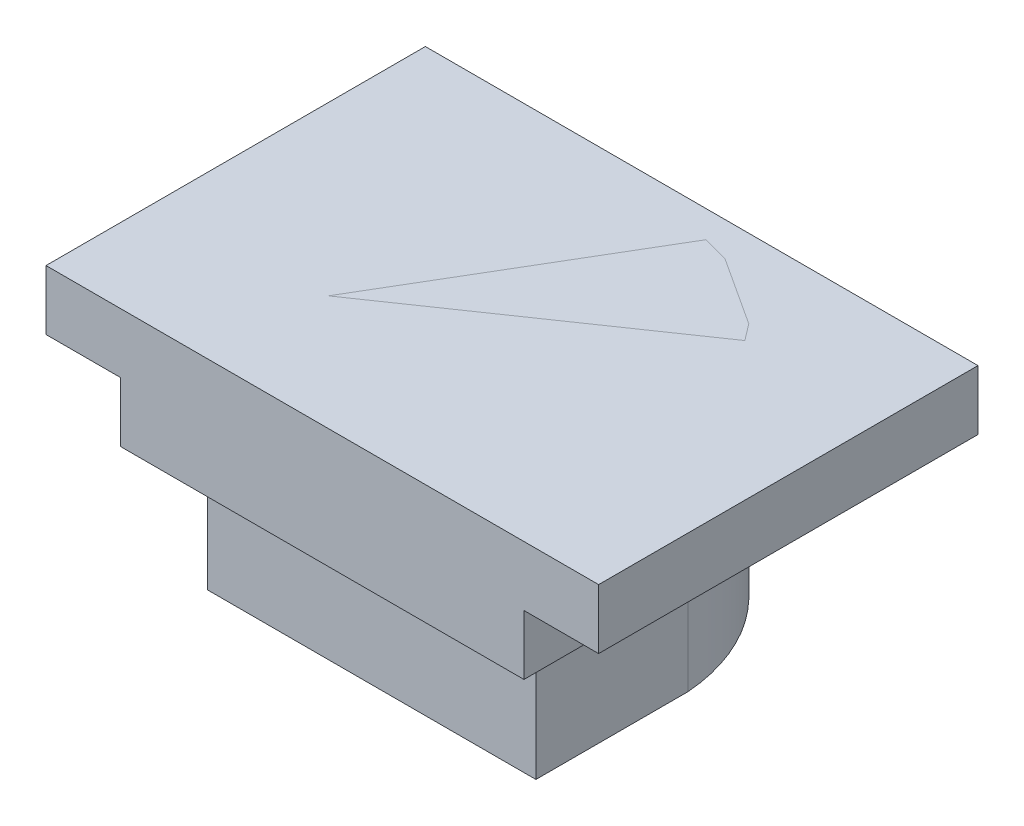
SolidWorks part; units mm, degrees
ref_plane "Front Plane" through (0, 0, 0) normal (0, 0, 1) x (1, 0, 0)
ref_plane "Top Plane" through (0, 0, 0) normal (0, 1, 0) x (1, 0, 0)
ref_plane "Right Plane" through (0, 0, 0) normal (1, 0, 0) x (0, 0, -1)
sketch "Sketch2" plane through (0, 0, 0) normal (0, 1, 0) x (1, 0, 0)
  line L0 (0, 2.8) -> (-6, 2.8) construction
  line L1 (0, 0) -> (-6, 0) construction
  line L2 (0, 0) -> (0, 2.8) construction
  line L3 (-2.5, 5.6) -> (-6, 5.6) construction
  line L4 (-6, 0) -> (-6, 5.6) construction
  line L5 (-6, 5.5) -> (-2.5, 5.5)
  line L6 (-0.1, 0) -> (-0.1, 2.5) construction
  line L7 (-6, 2.8) -> (-5.6, 2.8)
  line L8 (-5.6, 5.5) -> (-5.6, 0.25)
  line L9 (-5.6, 0.25) -> (-0.1, 0.25)
  line L10 (-0.1, 0.25) -> (-0.1, 2.8)
  arc A0 (0, 2.5) -> (-2.5, 5.6) centre (-2.9867, 2.6495) ccw construction
  arc A1 (-2.5, 5.5) -> (-0.1, 2.8) centre (-3.0813, 2.5666) cw
  dimension "D8" = 2.9904
  dimension "D9" = 2.9904
  dimension "D1" = 0.1
  dimension "D2" = 5.6
  dimension "D3" = 3.5
  dimension "D4" = 2.5
  dimension "D5" = 0.1
  dimension "D6" = 5.5
  dimension "D7" = 0.25
extrude "Boss-Extrude2" add sketch "Sketch2" along normal blind 2 contours A1 L5 L8 L9 L10 region at (-2.9874, 0, -2.7482)
sketch "Sketch3" plane through (0, 0, 0) normal (0, -1, 0) x (1, 0, 0)
  line L0 (-6, 0) -> (-6, 0.4) construction
  line L1 (-6, 0) -> (-6.4, 0) construction
  line L2 (-6.4, 0.4) -> (0.35, 0.4)
  line L3 (0.35, 0.4) -> (0.35, -2.75)
  line L4 (-6.4, 0.4) -> (-6.4, -5.95)
  line L5 (-6.4, -5.95) -> (-2.55, -5.95)
  line L7 (0, 0) -> (0, -2.8) construction
  line L8 (-2.5, -5.6) -> (-6, -5.6) construction
  arc A0 (-2.55, -5.95) -> (0.35, -2.75) centre (-3.0119, -2.6174) ccw
  dimension "D4" = 3.85
  dimension "D5" = 3.15
  dimension "D1" = 0.4
  dimension "D2" = 0.35
  dimension "D3" = 0.35
  dimension "D6" = 0.4
extrude "Boss-Extrude3" add sketch "Sketch3" along normal blind 1
sketch "Sketch4" plane through (0, -1, 0) normal (0, -1, 0) x (1, 0, 0)
  line L0 (-6.4, 0.4) -> (-6.4, -5.95) construction
  line L1 (-7.65, 0.4) -> (1.6, 0.4)
  line L2 (-7.65, 0.4) -> (-7.65, -5.95)
  line L3 (-7.65, -5.95) -> (1.6, -5.95)
  line L4 (1.6, 0.4) -> (1.6, -5.95)
  line L5 (0.35, 0.4) -> (0.35, -2.75) construction
  dimension "D1" = 1.25
  dimension "D2" = 1.25
  dimension "D3" = 6.35
extrude "Boss-Extrude4" add sketch "Sketch4" along normal blind 1
extrude "Boss-Extrude6" add sketch "Sketch3<3>" along direction (0, -1, 0) on the side of the normal offset from surface (3 mm away) 3 up to face at (-2.8138, 0, -2.8753)
sketch "Sketch3<3>" plane through (0, 0, 0) normal (0, -1, 0) x (1, 0, 0) same geometry as "Sketch3"
extrude "Boss-Extrude7" add sketch "Sketch2<5>" along direction (0, -1, 0) on the side against the normal offset from surface (5 mm away) 2 separate body contours A1 L5 L8 L9 L10 region at (-2.9874, 0, -2.7482) up to face at (-2.8138, -3, -2.8753) offset beyond the face yes
sketch "Sketch2<5>" plane through (0, 0, 0) normal (0, 1, 0) x (1, 0, 0) same geometry as "Sketch2"
extrude "Cut-Extrude1" cut sketch "Sketch3<4>" against normal blind 3 and the other way blind 1
sketch "Sketch3<4>" plane through (0, 0, 0) normal (0, -1, 0) x (1, 0, 0) same geometry as "Sketch3"
